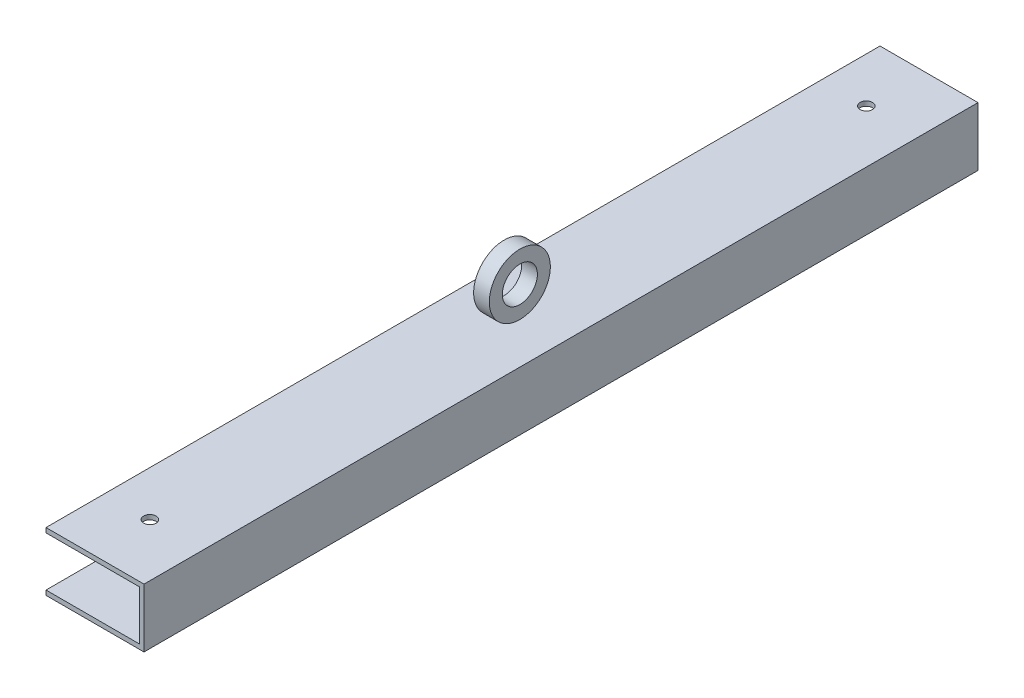
SolidWorks part; units mm, degrees
material "AISI 1020 Acero laminado en frío"
ref_plane "Alzado" through (0, 0, 0) normal (0, 0, 1) x (1, 0, 0)
ref_plane "Planta" through (0, 0, 0) normal (0, 1, 0) x (1, 0, 0)
ref_plane "Vista lateral" through (0, 0, 0) normal (1, 0, 0) x (0, 0, -1)
sketch "Croquis2" plane through (0, 0, 0) normal (0, 0, 1) x (1, 0, 0)
  line L1 (50, -30) -> (-50, -30)
  line L2 (50, -30) -> (50, 30)
  line L3 (50, 30) -> (-50, 30)
  line L4 (-50, -30) -> (-50, 30)
  line L5 (50, -30) -> (-50, 30) construction
  line L6 (50, 30) -> (-50, -30) construction
  point P0 (0, 0)
  point P6 (0, 30)
  dimension "D1" = 60
  dimension "D2" = 100
extrude "Saliente-Extruir1" add sketch "Croquis2" along normal mid plane 851
sketch "Croquis6" plane through (0, 0, 425.5) normal (0, 0, 1) x (1, 0, 0)
  line L4 (-50, 30) -> (-50, -30)
  line L5 (-50, -30) -> (50, -30)
  line L6 (50, -30) -> (50, 30)
  line L7 (50, 30) -> (-50, 30)
  line L8 (-50, 30) -> (-50, -30)
  line L9 (-50, -30) -> (50, -30)
  line L10 (50, -30) -> (50, 30)
  line L11 (50, 30) -> (-50, 30)
  line L16 (-45.2375, 25.2375) -> (-45.2375, -25.2375)
  line L17 (-45.2375, -25.2375) -> (45.2375, -25.2375)
  line L18 (45.2375, -25.2375) -> (45.2375, 25.2375)
  line L19 (45.2375, 25.2375) -> (-45.2375, 25.2375)
  line L20 (-45.2375, 25.2375) -> (-45.2375, -25.2375)
  line L21 (-45.2375, -25.2375) -> (45.2375, -25.2375)
  line L22 (45.2375, -25.2375) -> (45.2375, 25.2375)
  line L23 (45.2375, 25.2375) -> (-45.2375, 25.2375)
  dimension "D1" = 0
  dimension "D2" = 4.7625
extrude "Cortar-Extruir1" cut sketch "Croquis6" against normal blind 900 contours L22 L23 L20 L21 region at (0, 0, 425.5)
sketch "Croquis7" plane through (-50, 0, 0) normal (-1, 0, 0) x (0, 0, 1)
  line L0 (-425.5, 30) -> (-425.5, -30) construction
  line L1 (425.5, -25.2375) -> (-425.5, -25.2375)
  line L2 (425.5, -25.2375) -> (425.5, 25.2375)
  line L3 (425.5, 25.2375) -> (-425.5, 25.2375)
  line L4 (-425.5, -25.2375) -> (-425.5, 25.2375)
  line L5 (425.5, -25.2375) -> (-425.5, 25.2375) construction
  line L6 (425.5, 25.2375) -> (-425.5, -25.2375) construction
  line L7 (425.5, -30) -> (-425.5, -30) construction
  point P0 (0, 0)
  dimension "D1" = 4.7625
extrude "Cortar-Extruir2" cut sketch "Croquis7" against normal blind 20
sketch "Croquis8" plane through (0, 30, 0) normal (0, 1, 0) x (1, 0, 0)
  line L0 (-121.5247, 0) -> (93.3442, 0) construction
  line L1 (0, 497.4221) -> (0, -494.6167) construction
  line L4 (50, 425.5) -> (-50, 425.5) construction
  circle A0 centre (-4, 365.5) radius 6.35
  circle A1 centre (-4, -365.5) radius 6.35
  point P7 (0, 0)
  dimension "D1" = 12.7
  dimension "D2" = 60
  dimension "D3" = 4
extrude "Cortar-Extruir3" cut sketch "Croquis8" against normal blind 80
sketch "Croquis9" plane through (0, 0, 0) normal (1, 0, 0) x (0, 0, -1)
  line L0 (0, -85.0417) -> (0, 153.8885) construction
  line L1 (-425.5, 30) -> (425.5, 30) construction
  circle A0 centre (0, 61.15) radius 31.15
  circle A1 centre (0, 61.15) radius 17.9
  dimension "D1" = 62.3
  dimension "D2" = 35.8
extrude "Saliente-Extruir2" add sketch "Croquis9" along normal mid plane 16 separate body
